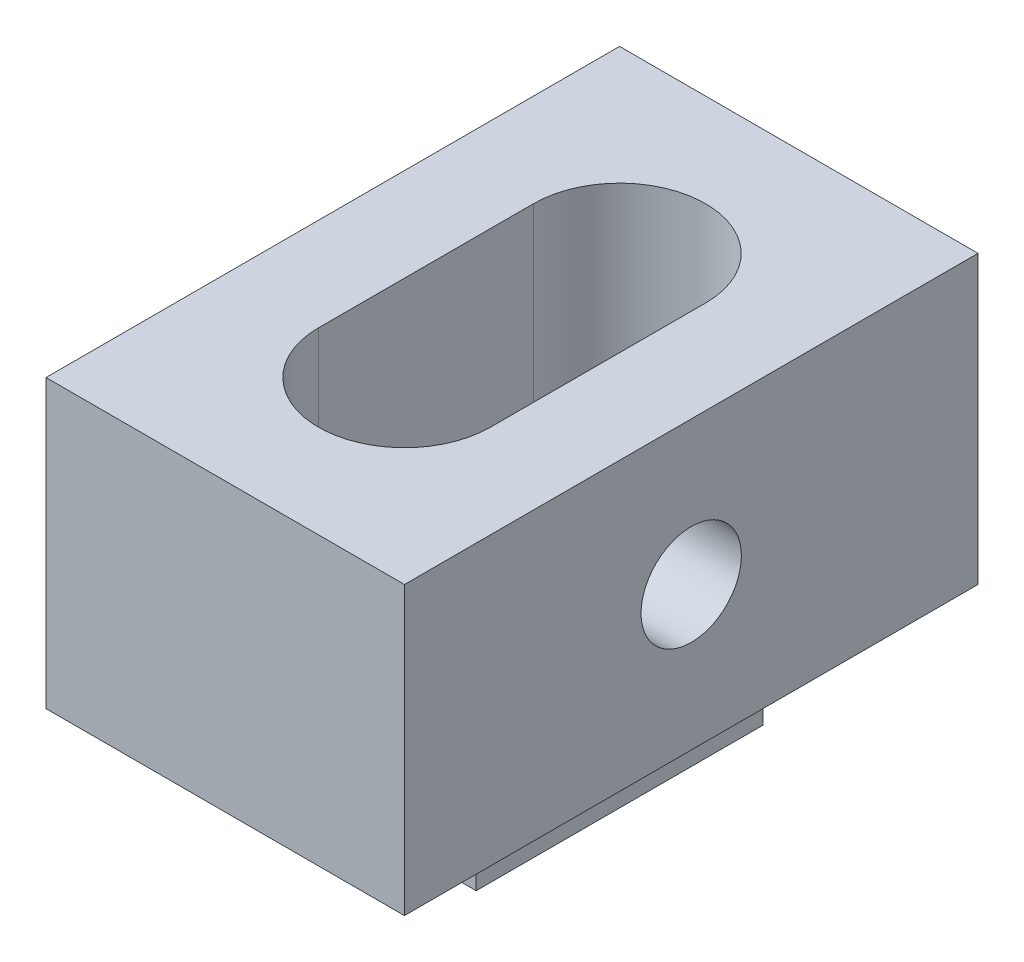
SolidWorks part; units mm, degrees
material "炭素鋼(普通)"
ref_plane "VERT" through (0, 0, 0) normal (0, 0, 1) x (1, 0, 0)
ref_plane "HOR" through (0, 0, 0) normal (0, 1, 0) x (1, 0, 0)
ref_plane "CTR" through (0, 0, 0) normal (1, 0, 0) x (0, 0, -1)
ref_axis "A_X" through (26.25, 0, 0) along (-1, 0, 0)
ref_axis "A_Y" through (0, 21.3, 0) along (0, -1, 0)
ref_axis "A_Z" through (0, 0, 22) along (0, 0, -1)
sketch3d "PNT_CG"
  point P0 (0, 0, 0)
sketch "Sketch1" plane through (0, 0, 0) normal (0, 0, 1) x (1, 0, 0)
  line L0 (0, -55) -> (0, 55) construction
  line L1 (0, 0) -> (25, 0)
  line L2 (0, 0) -> (0, 20)
  line L3 (0, 20) -> (25, 20)
  line L4 (25, 0) -> (25, 20)
  line L5 (55, 0) -> (-55, 0) construction
  dimension "D1" = 20
  dimension "D2" = 25
extrude "Boss-Extrude1" add sketch "Sketch1" along normal mid plane 40
sketch "Sketch2" plane through (0, 20, 0) normal (0, 1, 0) x (1, 0, 0)
  line L0 (6.5, 7.5) -> (6.5, -7.5)
  line L1 (18.5, 7.5) -> (18.5, -7.5)
  line L2 (12.5, 17.462) -> (12.5, -16.3737) construction
  line L3 (0, -14.3) -> (0, 14.3) construction
  line L4 (25, -20) -> (25, 20) construction
  line L5 (-18.4634, 0) -> (21.5366, 0) construction
  line L6 (-13.75, 0) -> (13.75, 0) construction
  arc A0 (6.5, 7.5) -> (18.5, 7.5) centre (12.5, 7.5) cw
  arc A1 (6.5, -7.5) -> (18.5, -7.5) centre (12.5, -7.5) ccw
  point P10 (6.5, 0)
  dimension "D3" = 6
  dimension "D1" = 12
  dimension "D2" = 15
extrude "Cut-Extrude1" cut sketch "Sketch2" against normal blind 18 contours A0 L1 A1 L0
sketch "Sketch3" plane through (25, 0, 0) normal (1, 0, 0) x (0, 0, -1)
  point P0 (0, 10)
  point P1 (0, 0)
hole_wizard "Hole1" positions "Sketch4" profile "Sketch5" legacy end condition up to next
sketch "Sketch4" plane through (25, 0, 0) normal (1, 0, 0) x (0, 0, -1)
  point P0 (0, 10)
sketch "Sketch5" plane through (25, 10, 0) normal (0, 1, 0) x (0, 0, -1)
  line L0 (0, 0) -> (0, 6.5)
  line L1 (0, 6.5) -> (3.5, 6.5)
  line L2 (3.5, 6.5) -> (3.5, 0)
  line L3 (3.5, 0) -> (0, 0)
  line L4 (0, 110) -> (0, -10) construction
  dimension "Diameter" = 7
  dimension "Depth" = 6.5
sketch "Sketch6" plane through (0, 0, 0) normal (0, 1, 0) x (1, 0, 0)
  line L0 (25, 20) -> (0, 20) construction
  line L1 (25, -20) -> (0, -20) construction
  line L2 (25, -20) -> (25, 20) construction
  line L3 (0, -20) -> (0, 20) construction
  line L4 (25, 20) -> (0, 20)
  line L5 (25, -20) -> (0, -20)
  line L6 (25, -20) -> (25, 20)
  line L7 (0, -20) -> (0, 20)
  line L13 (5.1436, 0) -> (19.8564, 0) construction
  line L14 (-13.75, 0) -> (13.75, 0) construction
  line L15 (12.5, 8.6238) -> (12.5, -8.6238) construction
  line L17 (20, -10) -> (5, -10)
  line L18 (25, 20) -> (0, 20)
  line L19 (0, 20) -> (0, -20)
  line L20 (0, -20) -> (25, -20)
  line L21 (25, -20) -> (25, 20)
  line L22 (25, 20) -> (0, 20)
  line L23 (0, 20) -> (0, -20)
  line L24 (0, -20) -> (25, -20)
  line L25 (25, -20) -> (25, 20)
  line L26 (20, -10) -> (20, 10)
  line L27 (20, 10) -> (5, 10)
  line L28 (5, -10) -> (5, 10)
  line L29 (20, -10) -> (5, 10) construction
  line L30 (20, 10) -> (5, -10) construction
  point P10 (12.5, 0)
  point P11 (12.5, 0)
  dimension "D2" = 20
  dimension "D3" = 15
  dimension "D1" = 0
extrude "Boss-Extrude2" add sketch "Sketch6" against normal blind 6 contours L17 L28 L27 L26
